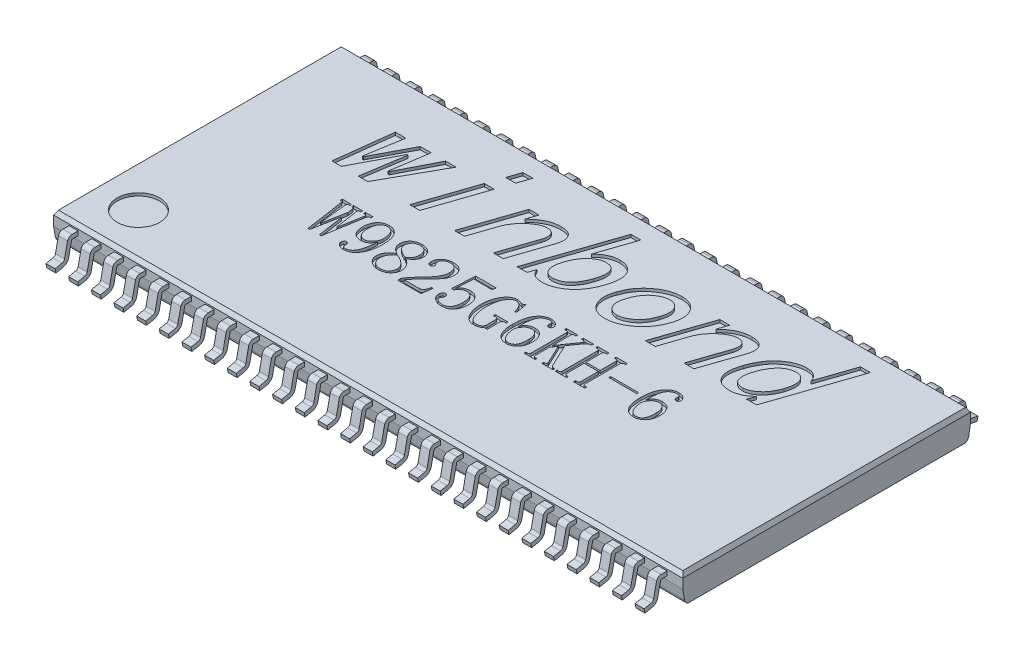
SolidWorks part; units mm, degrees
ref_plane "前视基准面" through (0, 0, 0) normal (0, 0, 1) x (1, 0, 0)
ref_plane "上视基准面" through (0, 0, 0) normal (0, 1, 0) x (1, 0, 0)
ref_plane "右视基准面" through (0, 0, 0) normal (1, 0, 0) x (0, 0, -1)
sketch "草图1" plane through (0, 0, 0) normal (0, 1, 0) x (1, 0, 0)
  line L1 (0, 0) -> (22.22, 0)
  line L2 (0, 0) -> (0, 10.16)
  line L3 (0, 10.16) -> (22.22, 10.16)
  line L4 (22.22, 0) -> (22.22, 10.16)
  dimension "D1" = 22.22
  dimension "D2" = 10.16
extrude "凸台-拉伸1" add sketch "草图1" along normal blind 1
sketch "草图2" plane through (0, 0, 0) normal (0, 0, 1) x (1, 0, 0)
  line L0 (11.11, 1.8672) -> (11.11, -0.4501) construction
  line L1 (22.22, 1) -> (22.22, 0) construction
  line L2 (0, 1) -> (0, 0) construction
  line L3 (0, 1) -> (22.22, 1) construction
  line L4 (10.95, 0.8) -> (11.27, 0.8)
  line L5 (10.95, 0.8) -> (10.95, 0.65)
  line L6 (10.95, 0.65) -> (11.27, 0.65)
  line L7 (11.27, 0.8) -> (11.27, 0.65)
  dimension "D1" = 0.32
  dimension "D2" = 0.15
  dimension "D3" = 0.2
ref_plane "基准面1" through (11.11, 0, 0) normal (1, 0, 0) x (0, 0, -1)
sketch "草图3" plane through (11.11, 0, 0) normal (1, 0, 0) x (0, 0, -1)
  line L0 (0, 0.725) -> (-0.2139, 0.725)
  line L1 (0, 0.8) -> (0, 0.65) construction
  line L2 (-0.3036, 0.6593) -> (-0.407, 0.1656)
  line L3 (-0.5535, 0.0255) -> (-0.8, -0.025)
  line L4 (0, 1.8672) -> (0, -0.4501) construction
  line L5 (0, 0) -> (10.16, 0) construction
  arc A0 (-0.2139, 0.725) -> (-0.3036, 0.6593) centre (-0.2139, 0.6309) ccw
  arc A1 (-0.407, 0.1656) -> (-0.5535, 0.0255) centre (-0.5824, 0.2024) cw
  dimension "D1" = 0.8
  dimension "D2" = 0.025
sweep "扫描1" add profiles "草图2" path "草图3"
pattern_linear "阵列(线性)1" count 14 spacing 0.8 along (-1, 0, 0) count 14 spacing 0.8 along (1, 0, 0) of "扫描1"
ref_plane "基准面2" through (0, 0, -5.08) normal (0, 0, 1) x (1, 0, 0)
mirror "镜向1" about plane through (0, 0, -5.08) normal (0, 0, 1) of "扫描1", "阵列(线性)1"
chamfer "倒角1" distance 0.15 angle 30 4 edges at (22.22, 1, -5.08) (11.11, 1, 0) (0, 1, -5.08) (11.11, 1, -10.16)
sketch "草图4" plane through (0, 0, 0) normal (-1, 0, 0) x (0, 0, 1)
  line L0 (-10.16, 0.5173) -> (-10.0968, 0.1504)
  line L1 (-10.16, 0.85) -> (-10.16, 0) construction
  line L2 (-10.16, 0) -> (0, 0) construction
  line L3 (-10.16, 0.5173) -> (-10.16, 0)
  line L4 (-10.16, 0) -> (-9.9771, 0)
  line L5 (-5.08, 1.7097) -> (-5.08, -1.0438) construction
  line L6 (-5.08, -0.4675) -> (-5.08, 0.4675) construction
  line L7 (0, 0.85) -> (0, 0) construction
  line L8 (0, 0) -> (-0.1829, 0)
  line L9 (0, 0.5173) -> (0, 0)
  line L10 (0, 0.5173) -> (-0.0632, 0.1504)
  arc A0 (-10.0968, 0.1504) -> (-9.9771, 0) centre (-9.8997, 0.1844) ccw
  arc A1 (-0.0632, 0.1504) -> (-0.1829, 0) centre (-0.2603, 0.1844) cw
  dimension "D1" = 0.2
  dimension "D2" = 0.5173
  dimension "D3" = 0.1829
  dimension "D4" = 0.1504
extrude "切除-拉伸1" cut sketch "草图4" against normal up to next
sketch "草图6" plane through (0, 1, 0) normal (0, 1, 0) x (1, 0, 0)
  text T0 "<i>winbond</i>\r\n" font "黑体" height 3
  text T1 "W9825G6KH-6" font "宋体" height 1.5
sketch "草图7" plane through (0, 1, 0) normal (0, 1, 0) x (1, 0, 0)
  circle A0 centre (1.5, 1.5) radius 0.75
  dimension "D1" = 1.5
  dimension "D2" = 1.5
  dimension "D3" = 1.5
extrude "切除-拉伸2" cut sketch "草图7" against normal blind 0.1
extrude "切除-拉伸3" cut sketch "草图6" against normal blind 0.1
